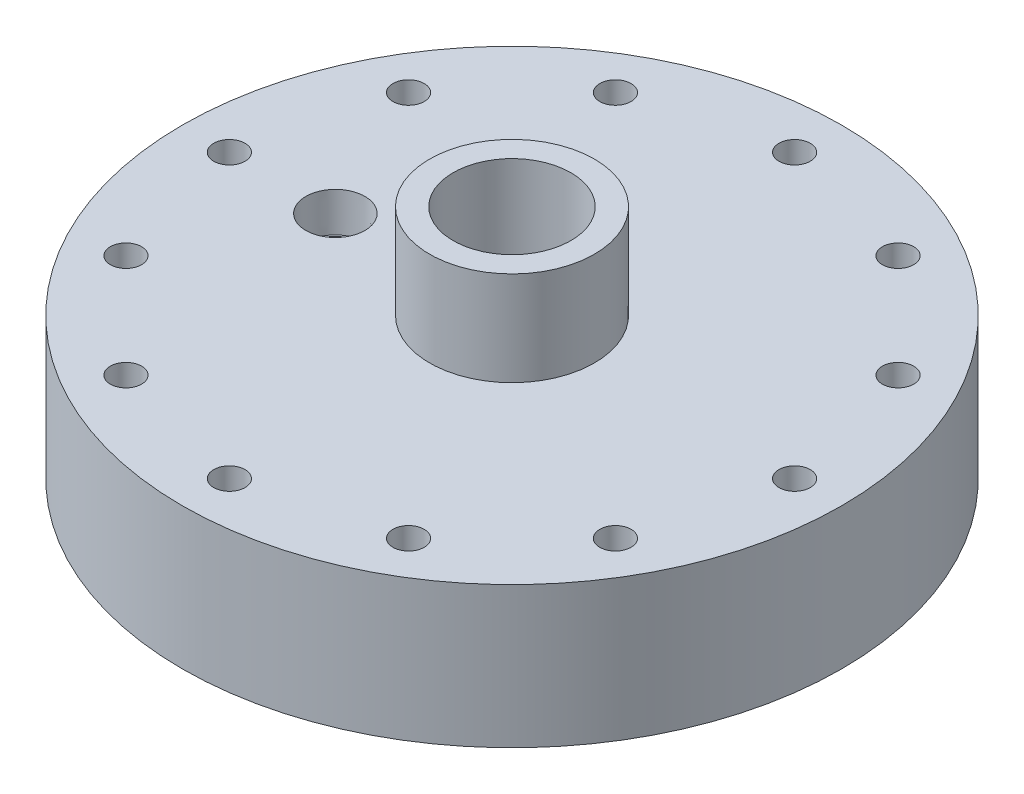
SolidWorks part; units mm, degrees
ref_plane "Front Plane" through (0, 0, 0) normal (0, 0, 1) x (1, 0, 0)
ref_plane "Top Plane" through (0, 0, 0) normal (0, 1, 0) x (1, 0, 0)
ref_plane "Right Plane" through (0, 0, 0) normal (1, 0, 0) x (0, 0, -1)
sketch "Sketch1" plane through (0, 0, 0) normal (0, 0, 1) x (1, 0, 0)
  line L0 (0, 0) -> (0, 51.199) construction
  line L1 (-62.2935, 0) -> (-88.9, 0)
  line L2 (-88.9, 0) -> (-88.9, 38.1)
  line L3 (-88.9, 38.1) -> (-22.225, 38.1)
  line L4 (-22.225, 38.1) -> (-22.225, 63.5)
  line L5 (-22.225, 63.5) -> (-15.875, 63.5)
  line L6 (-15.875, 63.5) -> (-15.875, 31.75)
  line L8 (-31.75, 31.75) -> (-15.875, 31.75)
  line L12 (-31.75, 31.75) -> (-31.75, 19.05)
  line L13 (-31.75, 19.05) -> (-38.1, 19.05)
  line L14 (-38.1, 19.05) -> (-38.1, 12.7)
  line L15 (-38.1, 12.7) -> (-57.15, 12.7)
  line L16 (-57.15, 12.7) -> (-57.15, 0)
  line L17 (-57.15, 0) -> (-58.7375, 0)
  line L18 (-58.7375, 0) -> (-58.7375, 2.54)
  line L19 (-58.7375, 2.54) -> (-62.2935, 2.54)
  line L20 (-62.2935, 2.54) -> (-62.2935, 0)
  dimension "D1" = 6.35
  dimension "D2" = 31.75
  dimension "D3" = 25.4
  dimension "D4" = 6.35
  dimension "D5" = 88.9
  dimension "D6" = 12.7
  dimension "D7" = 15.875
  dimension "D8" = 6.35
  dimension "D9" = 12.7
  dimension "D10" = 38.1
  dimension "D11" = 6.35
  dimension "D12" = 57.15
  dimension "D13" = 3.556
  dimension "D14" = 2.54
  dimension "D15" = 1.5875
revolve "Revolve1" add sketch "Sketch1" angle 360 about L0
hole_wizard "3/8 NPT Tapped Hole1" positions "Sketch2" profile "Sketch3" size "3/8" standard "ANSI Inch"
sketch "Sketch2" plane through (0, 38.1, 0) normal (0, 1, 0) x (1, 0, 0)
  point P0 (-47.625, 0)
  dimension "D1" = 47.625
sketch "Sketch3" plane through (-47.625, 38.1, 0) normal (1, 0, 0) x (0, 0, 1)
  line L0 (0, 0) -> (0, 29.6886)
  line L1 (7.1374, 25.4) -> (0, 29.6886)
  line L2 (-7.1374, 25.4) -> (0, 29.6886) construction
  line L3 (7.1374, 25.4) -> (7.1374, 10.414)
  line L4 (7.1374, 10.414) -> (7.6537, 10.414)
  line L5 (7.6537, 10.414) -> (7.9655, 0)
  line L6 (-7.6537, 10.414) -> (-7.9655, 0) construction
  line L7 (7.9655, 0) -> (0, 0)
  line L8 (0, -6.35) -> (0, 107.95) construction
  line L11 (-7.1374, 10.414) -> (-7.6537, 10.414) construction
  dimension "Tap Drill Dia." = 14.2748
  dimension "Tap Drill Depth" = 25.4
  dimension "Thread Dia." = 15.9311
  dimension "Thread Angle" = 3.43
  dimension "Thread Depth" = 10.414
  dimension "Drill Angle" = 118
cosmetic thread "Hole Thread1" parameters "D1"=10.414, "D2"=17.1495
hole_wizard "5/16 Clearance Hole1" positions "Sketch4" profile "Sketch6" hole size "5/16" standard "ANSI Inch" end condition through all
sketch "Sketch4" plane through (0, 38.1, 0) normal (0, 1, 0) x (1, 0, 0)
  point P0 (-76.2, 0)
  dimension "D1" = 76.2
sketch "Sketch6" plane through (-76.2, 38.1, 0) normal (1, 0, 0) x (0, 0, 1)
  line L0 (0, 0) -> (0, 38.1)
  line L1 (0, 38.1) -> (4.2164, 38.1)
  line L2 (4.2164, 38.1) -> (4.2164, 0)
  line L5 (4.2164, 0) -> (0, 0)
  line L11 (0, -6.35) -> (0, 107.95) construction
  dimension "Thru Hole Dia." = 8.4328
  dimension "Thru Hole Depth" = 38.1
pattern_circular "CirPattern1" count 12 over 360 about axis through (0, 0, 0) along (0, -1, 0) of "5/16 Clearance Hole1" reverse direction yes
